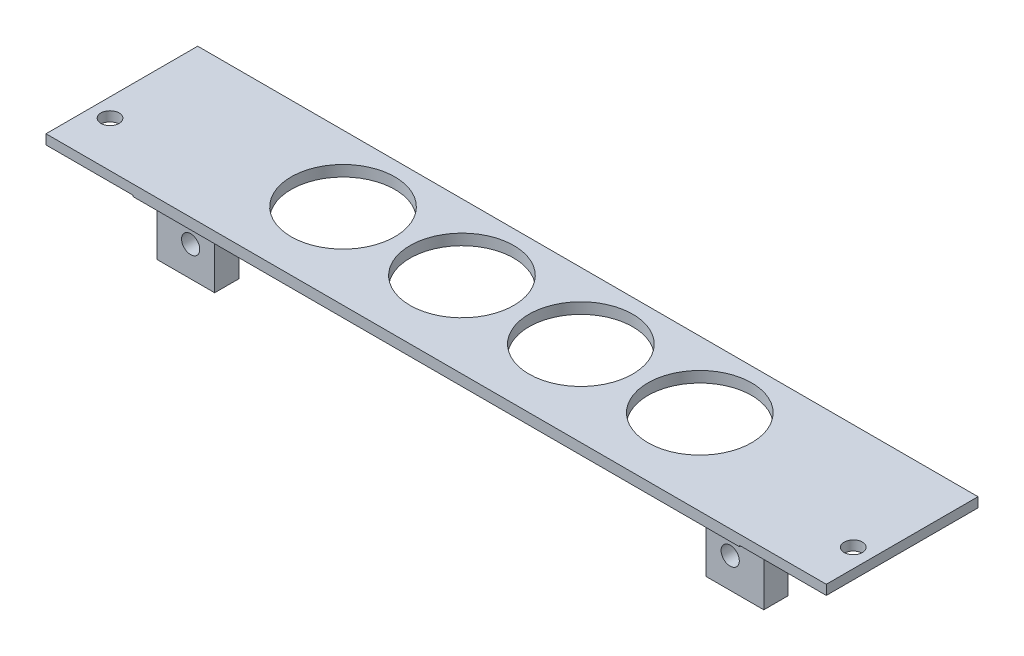
SolidWorks part; units mm, degrees
ref_plane "Front Plane" through (0, 0, 0) normal (0, 0, 1) x (1, 0, 0)
ref_plane "Top Plane" through (0, 0, 0) normal (0, 1, 0) x (1, 0, 0)
ref_plane "Right Plane" through (0, 0, 0) normal (1, 0, 0) x (0, 0, -1)
sketch "Sketch1" plane through (0, 0, 0) normal (0, 1, 0) x (1, 0, 0)
  line L5 (-64.3, 12.5) -> (64.3, 12.5)
  line L6 (-64.3, 12.5) -> (-64.3, -12.5)
  line L7 (-64.3, -12.5) -> (64.3, -12.5)
  line L8 (64.3, 12.5) -> (64.3, -12.5)
  line L9 (0, -12.5) -> (0, 12.5) construction
  line L10 (-64.3, 0) -> (64.3, 0) construction
  circle A0 centre (-61.25, -5) radius 1.5
  circle A1 centre (61.25, -5) radius 1.5
  circle A2 centre (-29.4, 1.55) radius 8.55
  circle A3 centre (-9.8, 1.55) radius 8.55
  circle A4 centre (9.8, 1.55) radius 8.55
  circle A5 centre (29.4, 1.55) radius 8.55
  point P0 (0, 0)
  point P19 (0, 0)
  point P20 (0, 0)
  point P21 (0, 0)
  point P22 (0, 0)
  dimension "D1" = 128.6
  dimension "D2" = 25
  dimension "D3" = 61.25
  dimension "D4" = 61.25
  dimension "D5" = 7.5
  dimension "D6" = 7.5
  dimension "D7" = 9.8
  dimension "D8" = 9.8
  dimension "D9" = 19.6
  dimension "D10" = 19.6
  dimension "D11" = 19.6
extrude "Boss-Extrude1" add sketch "Sketch1" along normal blind 1.6
ref_plane "PCB_back" through (0, -2.54, 0) normal (0, 1, 0) x (1, 0, 0)
ref_plane "PCB_top" through (0, 0, 8.5) normal (0, 0, 1) x (1, 0, 0)
sketch "Sketch3" plane through (0, 0, 0) normal (0, 1, 0) x (1, 0, 0)
  line L0 (64.3, 12.5) -> (-64.3, 12.5) construction
  line L1 (-50, 12.5) -> (50, 12.5)
  line L2 (-50, 12.5) -> (-50, -12.5)
  line L3 (-50, -12.5) -> (50, -12.5)
  line L4 (50, 12.5) -> (50, -12.5)
  line L5 (-64.3, -12.5) -> (64.3, -12.5) construction
  line L6 (-64.3, 12.5) -> (-64.3, -12.5) construction
  circle A0 centre (-29.4, 1.55) radius 8.55
  circle A1 centre (-9.8, 1.55) radius 8.55
  circle A2 centre (9.8, 1.55) radius 8.55
  circle A3 centre (29.4, 1.55) radius 8.55
  dimension "D1" = 100
  dimension "D2" = 14.3
extrude "Boss-Extrude4" add sketch "Sketch3" against normal blind 0.2
sketch "Sketch4" plane through (0, 0, 8.5) normal (0, 0, 1) x (1, 0, 0)
  line L0 (-50, -0.2) -> (50, -0.2) construction
  line L1 (-50, -0.2) -> (-40.5, -0.2)
  line L2 (-50, -0.2) -> (-50, -11.2)
  line L3 (-50, -11.2) -> (-40.5, -11.2)
  line L4 (-40.5, -0.2) -> (-40.5, -11.2)
  line L5 (50, -0.2) -> (40.5, -0.2)
  line L6 (50, -0.2) -> (50, -11.2)
  line L7 (50, -11.2) -> (40.5, -11.2)
  line L8 (40.5, -0.2) -> (40.5, -11.2)
  line L9 (0, -7.755) -> (0, 7.755) construction
  circle A0 centre (44.46, -6.24) radius 1.5
  circle A1 centre (-44.46, -6.24) radius 1.5
  dimension "D2" = 11
  dimension "D3" = 11
  dimension "D8" = 50
  dimension "D9" = 5.54
  dimension "D10" = 6.04
  dimension "D11" = 5.54
  dimension "D12" = 6.04
  dimension "D13" = 50
  dimension "D4" = 40.5
  dimension "D7" = 40.5
extrude "Boss-Extrude5" add sketch "Sketch4" against normal blind 4
fillet "Fillet1" radius 2 2 edges at (-45.25, -0.2, 4.5) (45.25, -0.2, 4.5)
equation "\"D8@Sketch1\"=\"D7@Sketch1\""
equation "\"D9@Sketch1\"=\"D7@Sketch1\" * 2"
equation "\"D10@Sketch1\"=\"D9@Sketch1\""
equation "\"D11@Sketch1\"=\"D9@Sketch1\""
equation "\"D7@Sketch4\"=\"D4@Sketch4\""
equation "\"D13@Sketch4\"=\"D8@Sketch4\""
equation "\"D9@Sketch4\"=\"D11@Sketch4\""
